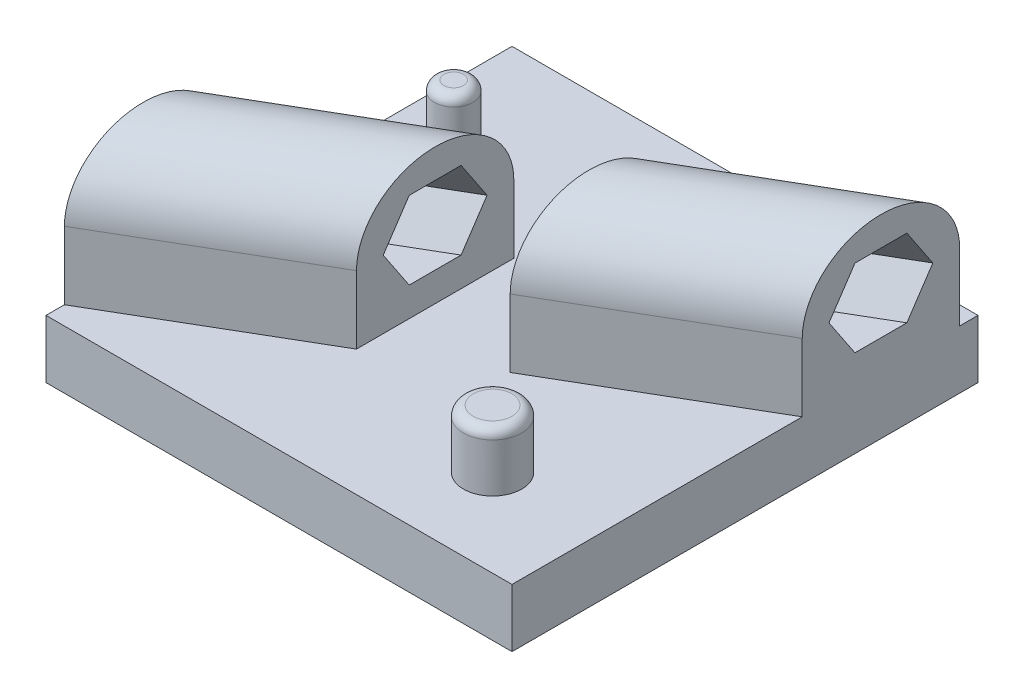
SolidWorks part; units mm, degrees
ref_plane "Front Plane" through (0, 0, 0) normal (0, 0, 1) x (1, 0, 0)
ref_plane "Top Plane" through (0, 0, 0) normal (0, 1, 0) x (1, 0, 0)
ref_plane "Right Plane" through (0, 0, 0) normal (1, 0, 0) x (0, 0, -1)
sketch "Sketch1" plane through (0, 0, 0) normal (0, 0, 1) x (1, 0, 0)
  line L0 (-137.9467, 0) -> (128.0407, 0) construction
  line L1 (0, 73.1907) -> (0, -56.8482) construction
  line L2 (120, 15) -> (-120, 15)
  line L7 (120, 15) -> (120, -15)
  line L8 (120, -15) -> (-120, -15)
  line L9 (-120, 15) -> (-120, -15)
  dimension "D1" = 240
  dimension "D2" = 30
extrude "Boss-Extrude2" add sketch "Sketch1" along normal mid plane 240
ref_point "Point3" parameters "D1"=50
ref_point "Point4" parameters "D1"=50
ref_axis "Axis3" through (70, 15, 120) along (-0.5039, 0, -0.8638)
ref_plane "Plane3" through (0, 0, 0) normal (0.8638, 0, -0.5039) x (-0.5039, 0, -0.8638)
sketch "Sketch6" plane through (0, 0, 0) normal (0.8638, 0, -0.5039) x (-0.5039, 0, -0.8638)
  line L0 (67.7294, 0) -> (-68.7556, 0) construction
  line L1 (0, 88.117) -> (0, -65.3004) construction
  line L2 (35, 0) -> (35, 50)
  line L3 (-35, 0) -> (-35, 50)
  line L4 (35, 0) -> (-35, 0)
  line L6 (23.094, 50) -> (11.547, 70)
  line L7 (11.547, 70) -> (-11.547, 70)
  line L8 (-11.547, 70) -> (-23.094, 50)
  line L9 (-23.094, 50) -> (-11.547, 30)
  line L10 (-11.547, 30) -> (11.547, 30)
  line L11 (11.547, 30) -> (23.094, 50)
  line L12 (-138.9244, 15) -> (138.9244, 15) construction
  arc A0 (35, 50) -> (-35, 50) centre (0, 50) ccw
  circle A1 centre (0, 50) radius 20 construction
  dimension "D4" = 35
  dimension "D1" = 35
  dimension "D2" = 40
  dimension "D3" = 70
extrude "Boss-Extrude3" add sketch "Sketch6" against normal up to surface and the other way up to surface up to face at (-120, 0, 0) other way up to face at (120, 0, 0)
ref_plane "Plane5" through (0, 0, -70) normal (0, 0, -1) x (-1, 0, 0)
sketch "Sketch7" plane through (0, 0, -70) normal (0, 0, -1) x (-1, 0, 0)
  line L0 (-25, 15) -> (25, 15)
  line L1 (-70, 15) -> (70, 15) construction
  line L2 (25, 15) -> (25, 85)
  line L3 (120, 85) -> (-120, 85) construction
  line L4 (25, 85) -> (-25, 85)
  line L5 (-25, 85) -> (-25, 15)
  line L6 (0, 96.7429) -> (0, -84.3936) construction
  dimension "D2" = 50
extrude "Cut-Extrude1" cut sketch "Sketch7" against normal blind 250
sketch "Sketch8" plane through (0, 15, 0) normal (0, 1, 0) x (1, 0, 0)
  line L0 (-120, -29.4804) -> (-120, 120) construction
  line L1 (120, 120) -> (-120, 120) construction
  circle A0 centre (-90, 60) radius 10
  circle A1 centre (65, -75) radius 15
  dimension "D5" = 30
  dimension "D6" = 20
  dimension "D1" = 30
  dimension "D2" = 60
  dimension "D3" = 45
  dimension "D4" = 55
extrude "Boss-Extrude4" add sketch "Sketch8" along normal blind 30
fillet "Fillet1" radius 5 2 edges at (50, 45, 75) (-100, 45, -60)
